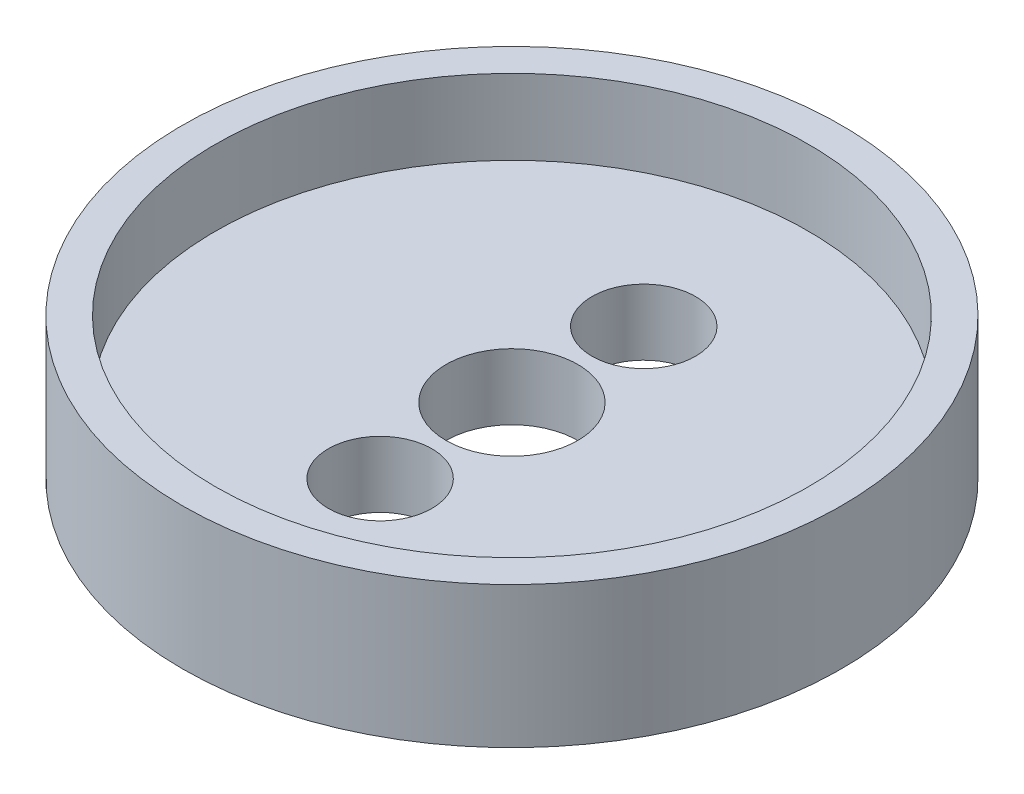
SolidWorks part; units mm, degrees
ref_plane "Front Plane" through (0, 0, 0) normal (0, 0, 1) x (1, 0, 0)
ref_plane "Top Plane" through (0, 0, 0) normal (0, 1, 0) x (1, 0, 0)
ref_plane "Right Plane" through (0, 0, 0) normal (1, 0, 0) x (0, 0, -1)
sketch "Sketch4" plane through (0, 0, 0) normal (0, 1, 0) x (1, 0, 0)
  line L0 (0, 3.5) -> (0, 7) construction
  line L1 (0, -3.5) -> (0, -7) construction
  circle A1 centre (0, 0) radius 17.5
  circle A4 centre (0, -7) radius 2.75
  circle A5 centre (0, 7) radius 2.75
  circle A6 centre (0, 0) radius 3.5 construction
  circle A7 centre (0, 0) radius 3.5
  dimension "D1" = 7
  dimension "D2" = 35
  dimension "D4" = 5.5
  dimension "D3" = 3.5
extrude "LidBase" add sketch "Sketch4" along normal blind 7.5
sketch "Sketch5" plane through (0, 7.5, 0) normal (0, 1, 0) x (1, 0, 0)
  circle A1 centre (0, 0) radius 15.75
  dimension "D1" = 31.5
extrude "LidGrooves" cut sketch "Sketch5" against normal blind 4
